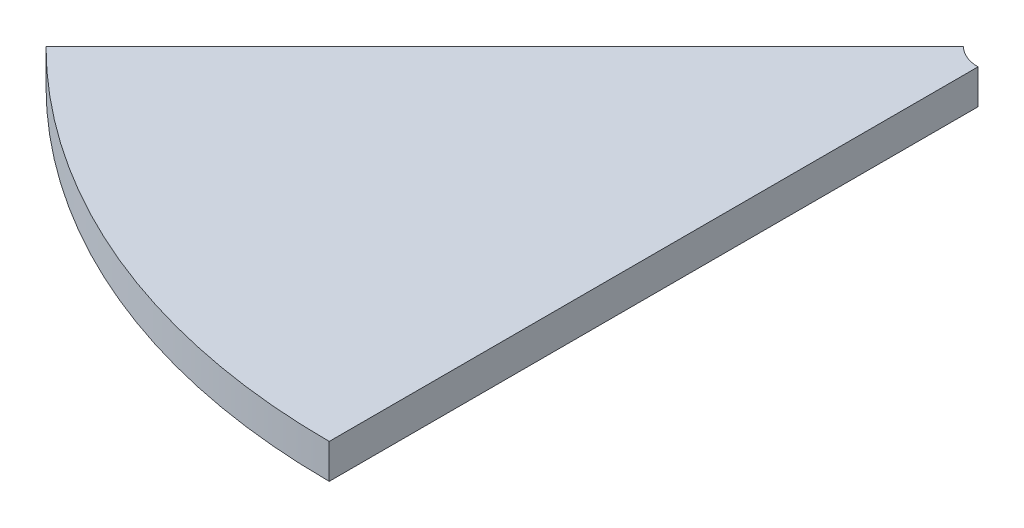
SolidWorks part; units mm, degrees
ref_plane "Front Plane" through (0, 0, 0) normal (0, 0, 1) x (1, 0, 0)
ref_plane "Top Plane" through (0, 0, 0) normal (0, 1, 0) x (1, 0, 0)
ref_plane "Right Plane" through (0, 0, 0) normal (1, 0, 0) x (0, 0, -1)
sketch "Sketch1" plane through (0, 0, 0) normal (0, 1, 0) x (1, 0, 0)
  line L0 (-14.3157, -14.3157) -> (-279.4808, -279.4808)
  line L2 (0, 78.7678) -> (0, 0) construction
  line L3 (0, -395.2455) -> (0, -20.2455)
  line L4 (0, -20.2455) -> (0, -764.7566) construction
  arc A0 (-14.3157, -14.3157) -> (0, -20.2455) centre (0, 0) ccw
  arc A1 (-279.4808, -279.4808) -> (0, -395.2455) centre (0, 0) ccw
  dimension "D1" = 375
  dimension "D3" = 45
extrude "Boss-Extrude1" add sketch "Sketch1" along normal blind 20
